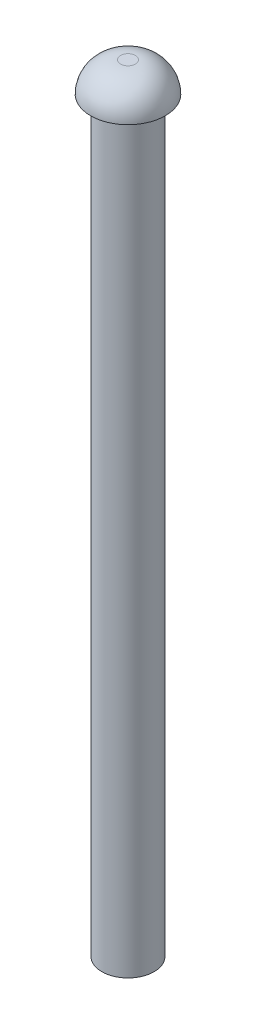
SolidWorks part; units mm, degrees
ref_plane "Front Plane" through (0, 0, 0) normal (0, 0, 1) x (1, 0, 0)
ref_plane "Top Plane" through (0, 0, 0) normal (0, 1, 0) x (1, 0, 0)
ref_plane "Right Plane" through (0, 0, 0) normal (1, 0, 0) x (0, 0, -1)
sketch "Sketch1" plane through (0, 0, 0) normal (0, 1, 0) x (1, 0, 0)
  circle A0 centre (0, 0) radius 3.5
  dimension "D1" = 7
extrude "Boss-Extrude1" add sketch "Sketch1" against normal blind 100
sketch "Sketch2" plane through (0, 0, 0) normal (0, 1, 0) x (1, 0, 0)
  circle A0 centre (0, 0) radius 5
  dimension "D1" = 10
extrude "Boss-Extrude2" add sketch "Sketch2" along normal blind 4
fillet "Fillet3" radius 4 1 edges at (0, 4, 5)
